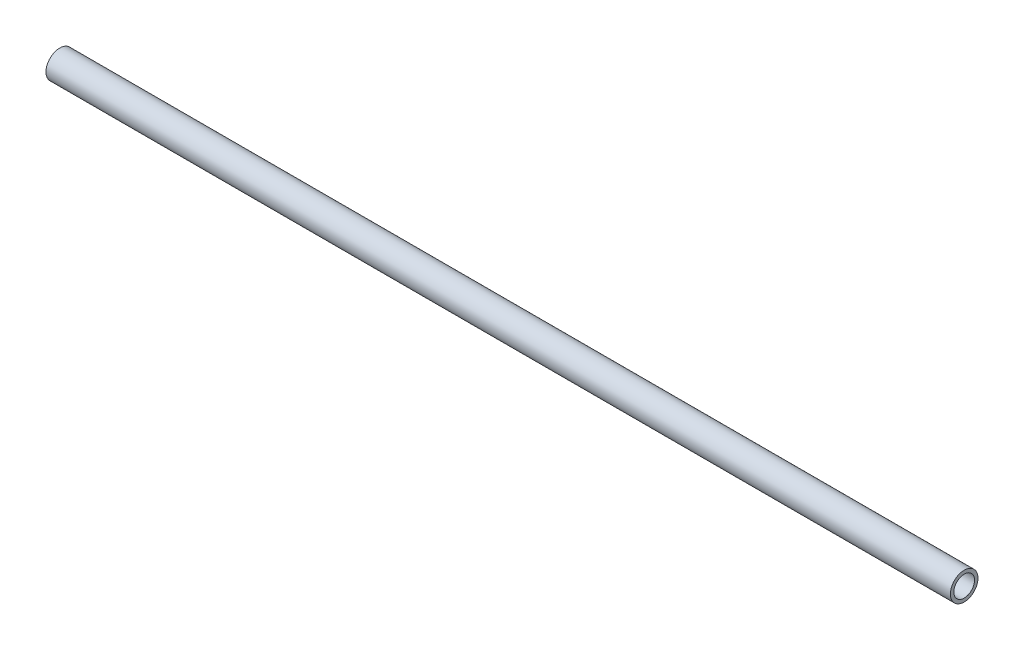
SolidWorks part; units mm, degrees
ref_plane "Front Plane" through (0, 0, 0) normal (0, 0, 1) x (1, 0, 0)
ref_plane "Top Plane" through (0, 0, 0) normal (0, 1, 0) x (1, 0, 0)
ref_plane "Right Plane" through (0, 0, 0) normal (1, 0, 0) x (0, 0, -1)
sketch "Sketch1" plane through (0, 0, 0) normal (1, 0, 0) x (0, 0, -1)
  circle A0 centre (0, 0) radius 3
  circle A1 centre (0, 0) radius 4
  dimension "D1" = 6
  dimension "D2" = 8
extrude "Boss-Extrude1" add sketch "Sketch1" along normal blind 262
